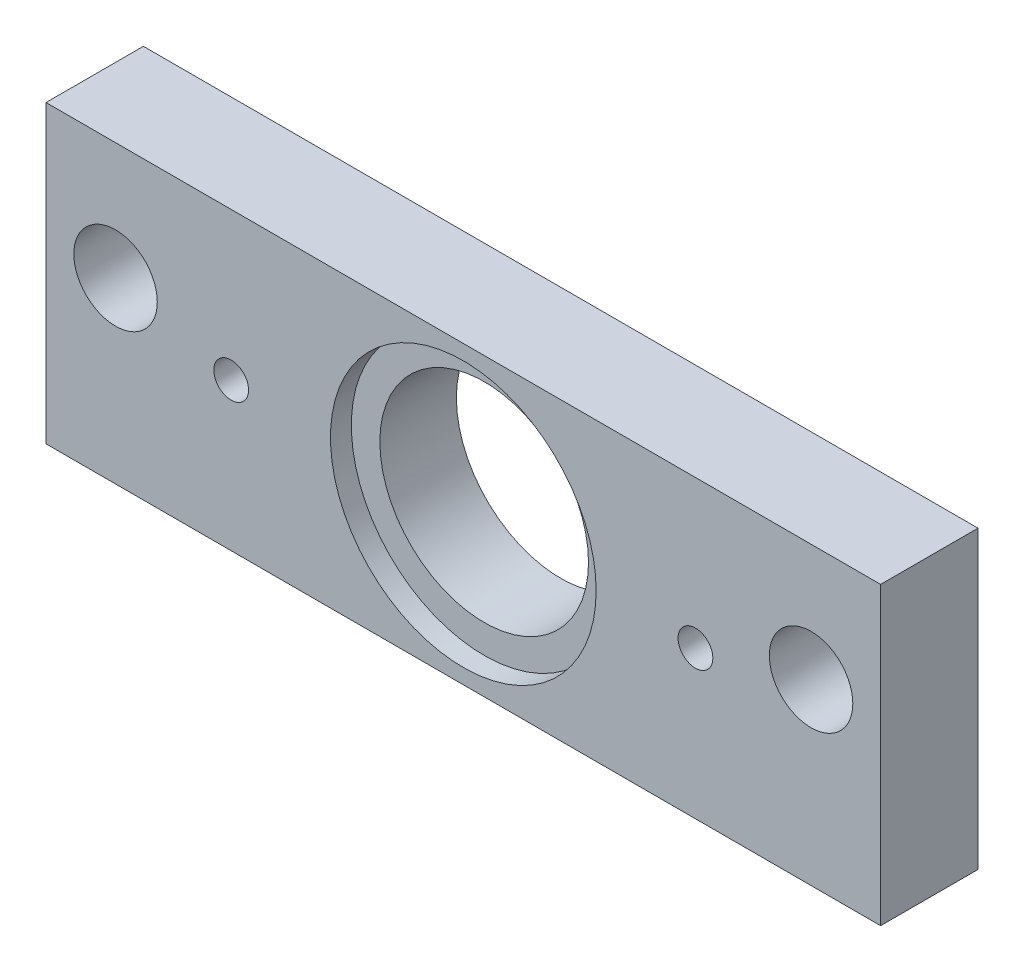
SolidWorks part; units mm, degrees
ref_plane "Front Plane" through (0, 0, 0) normal (0, 0, 1) x (1, 0, 0)
ref_plane "Top Plane" through (0, 0, 0) normal (0, 1, 0) x (1, 0, 0)
ref_plane "Right Plane" through (0, 0, 0) normal (1, 0, 0) x (0, 0, -1)
sketch "Sketch1" plane through (0, 0, 0) normal (0, 0, 1) x (1, 0, 0)
  line L1 (-60, -21.25) -> (60, -21.25)
  line L2 (-60, -21.25) -> (-60, 21.25)
  line L3 (-60, 21.25) -> (60, 21.25)
  line L4 (60, -21.25) -> (60, 21.25)
  line L5 (-60, -21.25) -> (60, 21.25) construction
  line L6 (-60, 21.25) -> (60, -21.25) construction
  point P0 (0, 0)
  dimension "D1" = 120
  dimension "D2" = 42.5
extrude "Boss-Extrude1" add sketch "Sketch1" along normal mid plane 14
sketch "Sketch2" plane through (0, 0, 7) normal (0, 0, 1) x (1, 0, 0)
  circle A0 centre (0, 0) radius 19.1
  dimension "D1" = 38.2
extrude "Cut-Extrude1" cut sketch "Sketch2" against normal blind 3
sketch "Sketch3" plane through (0, 0, 4) normal (0, 0, 1) x (1, 0, 0)
  circle A0 centre (0, 0) radius 15
extrude "Cut-Extrude2" cut sketch "Sketch3" against normal through all
sketch "Sketch4" plane through (0, 0, 7) normal (0, 0, 1) x (1, 0, 0)
  circle A0 centre (-33.375, 0) radius 2.5
  circle A1 centre (33.375, 0) radius 2.5
  dimension "D1" = 5
  dimension "D2" = 5
  dimension "D3" = 33.375
  dimension "D4" = 33.375
extrude "Cut-Extrude3" cut sketch "Sketch4" against normal through all
sketch "Sketch5" plane through (0, 0, 7) normal (0, 0, 1) x (1, 0, 0)
  line L0 (-40.6477, 4.4) -> (36.4799, 4.4) construction
  circle A0 centre (-50, 4.4) radius 6
  circle A1 centre (50, 4.4) radius 6
  dimension "D1" = 12
  dimension "D2" = 12
  dimension "D4" = 50
  dimension "D3" = 50
  dimension "D5" = 4.4
extrude "Cut-Extrude4" cut sketch "Sketch5" against normal through all
sketch "Sketch6" plane through (0, -21.25, 0) normal (0, -1, 0) x (1, 0, 0)
  line L0 (-60, 0) -> (60, 0) construction
  line L1 (-60, 7) -> (-60, -7) construction
  line L2 (60, 7) -> (60, -7) construction
  circle A0 centre (-50, 0) radius 2.5
  circle A1 centre (-25, 0) radius 2.5
  circle A2 centre (25, 0) radius 2.5
  circle A3 centre (50, 0) radius 2.5
  circle A4 centre (-37.5, 0) radius 1.25
  circle A5 centre (37.5, 0) radius 1.25
  dimension "D1" = 5
  dimension "D2" = 5
  dimension "D3" = 5
  dimension "D4" = 5
  dimension "D5" = 10
  dimension "D9" = 2.5
  dimension "D10" = 2.5
  dimension "D11" = 22.5
  dimension "D12" = 22.5
  dimension "D6" = 35
  dimension "D7" = 10
  dimension "D8" = 35
extrude "Cut-Extrude5" cut sketch "Sketch6" against normal blind 10
equation "\"D4@Sketch4\"=\"D3@Sketch4\""
